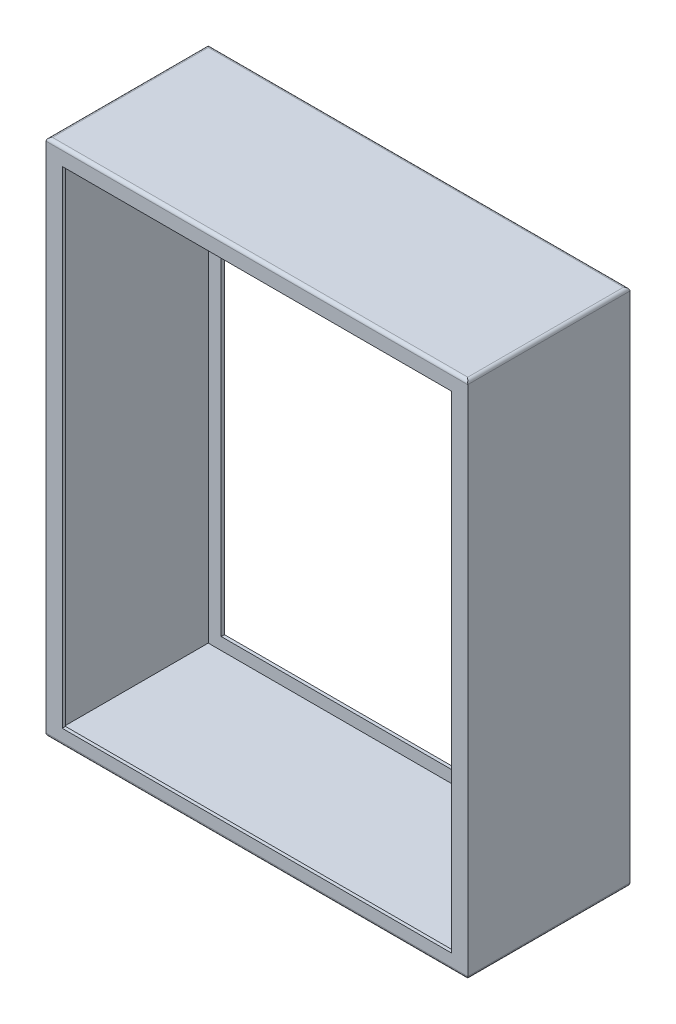
SolidWorks part; units mm, degrees
ref_plane "Front Plane" through (0, 0, 0) normal (0, 0, 1) x (1, 0, 0)
ref_plane "Top Plane" through (0, 0, 0) normal (0, 1, 0) x (1, 0, 0)
ref_plane "Right Plane" through (0, 0, 0) normal (1, 0, 0) x (0, 0, -1)
sketch "Sketch2" plane through (0, 0, 0) normal (0, 0, 1) x (1, 0, 0)
  line L1 (0, 0) -> (330.2, 0)
  line L2 (0, 0) -> (0, 406.4)
  line L3 (0, 406.4) -> (330.2, 406.4)
  line L4 (330.2, 0) -> (330.2, 406.4)
  dimension "D1" = 330.2
  dimension "D2" = 406.4
extrude "Boss-Extrude1" add sketch "Sketch2" along normal blind 127
fillet "Fillet1" radius 2.54 4 edges at (330.2, 406.4, 63.5) (165.1, 406.4, 127) (0, 406.4, 63.5) (165.1, 406.4, 0)
fillet "Fillet2" radius 2.54 4 edges at (0, 0, 63.5) (165.1, 0, 127) (330.2, 0, 63.5) (165.1, 0, 0)
sketch "Sketch3" plane through (0, 0, 127) normal (0, 0, 1) x (1, 0, 0)
  line L0 (0, 0) -> (330.2, 2.54) construction
  line L1 (165.1, 1.27) -> (165.1, 403.86) construction
  line L2 (330.2, 403.86) -> (0, 403.86) construction
  line L3 (165.1, 202.565) -> (0, 203.2) construction
  line L4 (0, 403.86) -> (0, 2.54) construction
  line L5 (0, 203.2) -> (330.2, 203.2) construction
  line L6 (330.2, 2.54) -> (330.2, 403.86) construction
  line L8 (12.7, 393.065) -> (317.5, 393.065)
  line L9 (12.7, 393.065) -> (12.7, 12.065)
  line L10 (12.7, 12.065) -> (317.5, 12.065)
  line L11 (317.5, 393.065) -> (317.5, 12.065)
  line L12 (12.7, 393.065) -> (317.5, 12.065) construction
  line L13 (12.7, 12.065) -> (317.5, 393.065) construction
  dimension "D1" = 304.8
  dimension "D2" = 381
extrude "Cut-Extrude1" cut sketch "Sketch3" against normal blind 127
shell "Shell4" thickness 2.54 removed face at (317.5, 202.565, 63.5) removed face at (165.1, 393.065, 63.5) removed face at (165.1, 12.065, 63.5) removed face at (12.7, 202.565, 63.5)
sketch "Sketch5" plane through (0, 0, 0) normal (-1, 0, 0) x (0, 0, 1)
  circle A0 centre (74.8759, 122.8945) radius 13.8368
